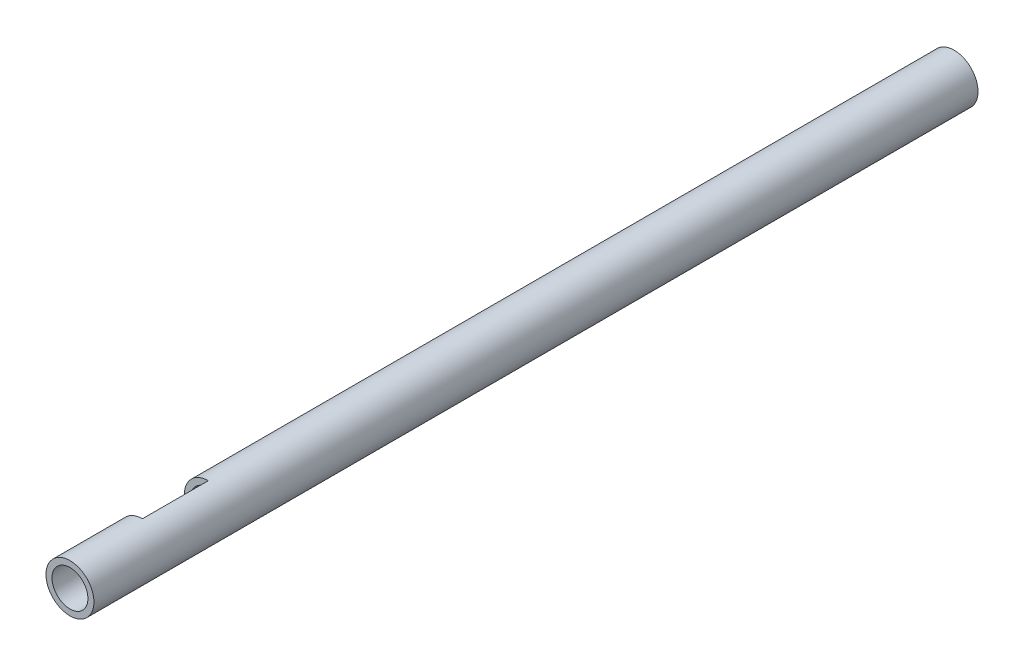
SolidWorks part; units mm, degrees
ref_plane "Front Plane" through (0, 0, 0) normal (0, 0, 1) x (1, 0, 0)
ref_plane "Top Plane" through (0, 0, 0) normal (0, 1, 0) x (1, 0, 0)
ref_plane "Right Plane" through (0, 0, 0) normal (1, 0, 0) x (0, 0, -1)
sketch "Sketch1" plane through (0, 0, 0) normal (1, 0, 0) x (0, 0, -1)
  line L0 (0, 0) -> (-101.6858, 0) construction
  line L2 (0, 20) -> (-738, 20)
  line L3 (0, 20) -> (0, 15)
  line L4 (0, 15) -> (-738, 15)
  line L5 (-738, 20) -> (-738, 15)
  dimension "D1" = 738
  dimension "D2" = 30
  dimension "D3" = 40
revolve "Revolve1" add sketch "Sketch1" angle 360 about L0
sketch "Sketch2" plane through (0, 0, 0) normal (0, 1, 0) x (1, 0, 0)
  line L0 (-37.7148, -650) -> (-87.2485, -650) construction
  line L1 (-37.7148, -707.5) -> (0, -707.5) construction
  line L2 (-37.7148, -707.5) -> (-37.7148, -592.5) construction
  line L3 (-37.7148, -592.5) -> (0, -592.5) construction
  line L4 (0, -707.5) -> (0, -592.5) construction
  line L5 (68, -592.5) -> (17, -592.5) construction
  line L6 (68, -707.5) -> (17, -707.5) construction
  line L7 (-37.7148, -622.5) -> (0, -622.5)
  line L8 (-37.7148, -622.5) -> (-37.7148, -677.5)
  line L9 (-37.7148, -677.5) -> (0, -677.5)
  line L10 (0, -622.5) -> (0, -677.5)
  point P13 (-37.7148, -650)
  dimension "D1" = 55
extrude "Cut-Extrude1" cut sketch "Sketch2" against normal through all and the other way through all
